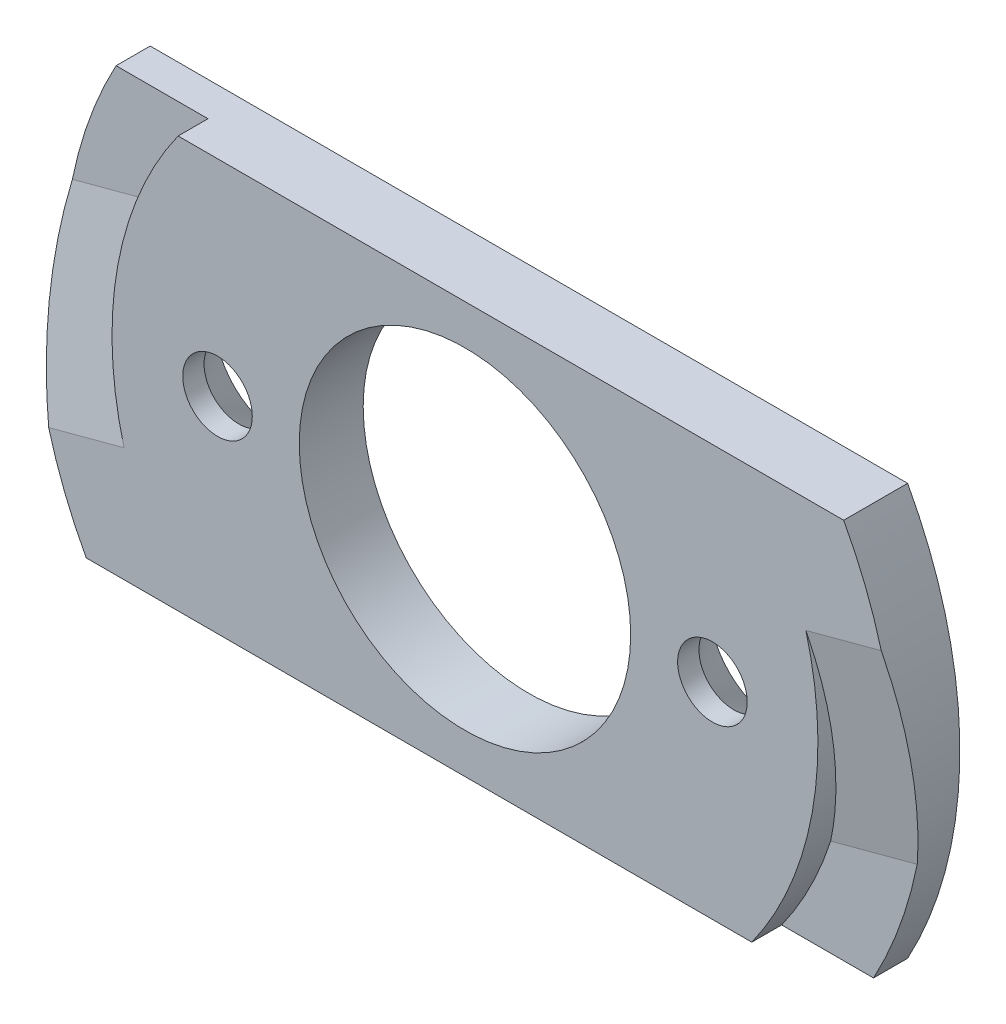
SolidWorks part; units mm, degrees
ref_plane "Front Plane" through (0, 0, 0) normal (0, 0, 1) x (1, 0, 0)
ref_plane "Top Plane" through (0, 0, 0) normal (0, 1, 0) x (1, 0, 0)
ref_plane "Right Plane" through (0, 0, 0) normal (1, 0, 0) x (0, 0, -1)
sketch "Sketch1" plane through (0, 0, 0) normal (0, 0, 1) x (1, 0, 0)
  line L0 (0, 9.65) -> (0, -9.65) construction
  line L5 (-19.531, -5.2333) -> (19.531, 5.2333)
  line L6 (-17.7687, -9.65) -> (17.7687, -9.65)
  line L11 (-20.22, 0) -> (20.22, 0) construction
  line L12 (-17.7687, 9.65) -> (17.7687, 9.65)
  circle A2 centre (-11.61, 0) radius 1.6319
  circle A3 centre (11.61, 0) radius 1.6319
  circle A4 centre (0, 0) radius 7.775
  arc A5 (-17.7687, 9.65) -> (-17.7687, -9.65) centre (0, 0) ccw
  arc A6 (-13.4578, 9.65) -> (-13.4578, -9.65) centre (0, 0) ccw
  arc A7 (17.7687, -9.65) -> (17.7687, 9.65) centre (0, 0) ccw
  arc A8 (13.4578, -9.65) -> (13.4578, 9.65) centre (0, 0) ccw
  point P5 (0, 0)
  point P6 (18.8791, 7.2407)
  dimension "D1" = 20.22
  dimension "D2" = 16.56
  dimension "D3" = 15.55
  dimension "D5" = 3.2639
  dimension "D6" = 15
  dimension "D4" = 23.22
  dimension "D9" = 19.3
extrude "Boss-Extrude1" add sketch "Sketch1" along normal blind 3 contours L6 A8 L12 A6 A2 A3 A4 | L5 A8 L12 A6 A4 A2 | A6 L5 A5 L6 | A8 L5 A7 L12 region at (-16.7509, -7.2494, 0) region at (-15.9436, 2.9036, 0) region at (-11.6612, -3.4912, 0) region at (16.7509, 7.2494, 0)
extrude "Boss-Extrude2" add sketch "Sketch1<3>" along normal blind 1.6 contours L11 A5 L6 A6 | A5 L11 A6 L12 | L11 A8 L6 A7 | A8 L11 A7 L12 region at (-17.7085, 2.5897, 0) region at (-16.7509, -7.2494, 0) region at (16.7509, 7.2494, 0) region at (17.7085, -2.5897, 0)
sketch "Sketch1<3>" plane through (0, 0, 0) normal (0, 0, 1) x (1, 0, 0) same geometry as "Sketch1"
chamfer "Chamfer1" distance 2 distance2 1.5 2 edges at (13.2419, 0, 0) (-9.9781, 0, 0) first distance on face at (13.2419, 0, 3) first distance on face at (-9.9781, 0, 3)
chamfer "Chamfer2" distance 1.4 distance2 9 1 edges at (-17.7634, -4.7597, 1.6) first distance on face at (-17.7634, -4.7597, 2.3)
chamfer "Chamfer3" distance 9 distance2 1.4 1 edges at (17.7634, 4.7597, 1.6) first distance on face at (17.4371, -2.5588, 1.6)
